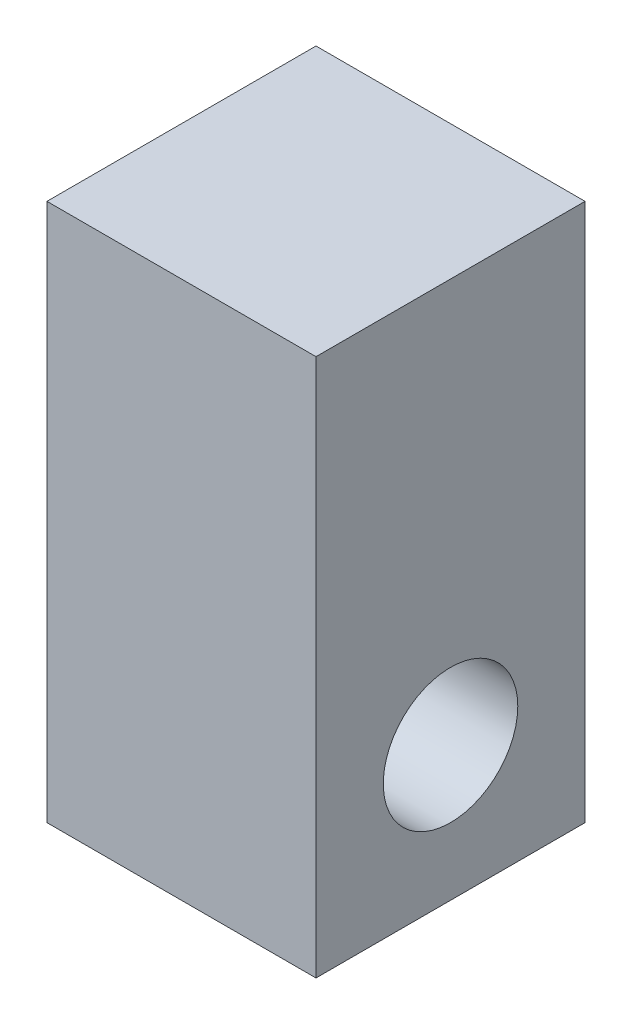
SolidWorks part; units mm, degrees
ref_plane "Front Plane" through (0, 0, 0) normal (0, 0, 1) x (1, 0, 0)
ref_plane "Top Plane" through (0, 0, 0) normal (0, 1, 0) x (1, 0, 0)
ref_plane "Right Plane" through (0, 0, 0) normal (1, 0, 0) x (0, 0, -1)
sketch "Sketch1" plane through (0, 0, 0) normal (0, 1, 0) x (1, 0, 0)
  line L1 (-12.7, 12.7) -> (12.7, 12.7)
  line L2 (-12.7, 12.7) -> (-12.7, -12.7)
  line L3 (-12.7, -12.7) -> (12.7, -12.7)
  line L4 (12.7, 12.7) -> (12.7, -12.7)
  line L5 (-12.7, 12.7) -> (12.7, -12.7) construction
  line L6 (-12.7, -12.7) -> (12.7, 12.7) construction
  point P0 (0, 0)
  dimension "D1" = 25.4
  dimension "D2" = 25.4
extrude "Boss-Extrude1" add sketch "Sketch1" along normal blind 50.8
sketch "Sketch2" plane through (12.7, 0, 0) normal (1, 0, 0) x (0, 0, -1)
  line L0 (-12.7, 0) -> (12.7, 0) construction
  circle A0 centre (0, 12.7) radius 6.35
  point P4 (0, 0)
  dimension "D1" = 12.7
  dimension "D2" = 12.7
extrude "Cut-Extrude1" cut sketch "Sketch2" against normal through all
